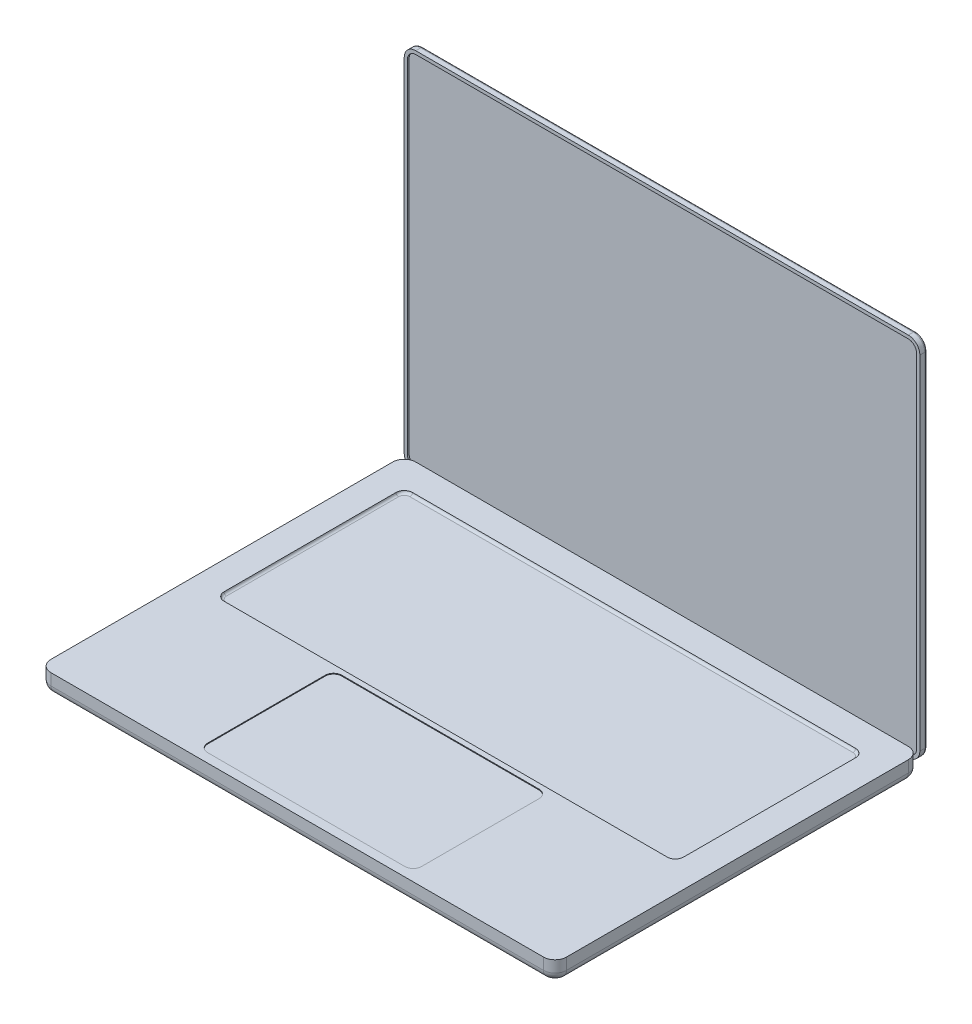
SolidWorks part; units mm, degrees
ref_plane "Front Plane" through (0, 0, 0) normal (0, 0, 1) x (1, 0, 0)
ref_plane "Top Plane" through (0, 0, 0) normal (0, 1, 0) x (1, 0, 0)
ref_plane "Right Plane" through (0, 0, 0) normal (1, 0, 0) x (0, 0, -1)
sketch "Sketch1" plane through (0, 0, 0) normal (0, 1, 0) x (1, 0, 0)
  line L1 (-149.337, -110.617) -> (149.337, -110.617)
  line L2 (-156.337, -103.617) -> (-156.337, 103.617)
  line L3 (-149.337, 110.617) -> (149.337, 110.617)
  line L4 (156.337, -103.617) -> (156.337, 103.617)
  line L5 (-156.337, -110.617) -> (156.337, 110.617) construction
  line L6 (-156.337, 110.617) -> (156.337, -110.617) construction
  arc A0 (149.337, 110.617) -> (156.337, 103.617) centre (149.337, 103.617) cw
  arc A1 (149.337, -110.617) -> (156.337, -103.617) centre (149.337, -103.617) ccw
  arc A2 (-149.337, -110.617) -> (-156.337, -103.617) centre (-149.337, -103.617) cw
  arc A3 (-156.337, 103.617) -> (-149.337, 110.617) centre (-149.337, 103.617) cw
  point P0 (0, 0)
  dimension "D3" = 7
  dimension "D1" = 221.234
  dimension "D2" = 312.674
extrude "Boss-Extrude1" add sketch "Sketch1" along normal blind 12
sketch "Sketch2" plane through (0, 0, -110.617) normal (0, 0, -1) x (-1, 0, 0)
  line L0 (0, 0) -> (0, 12) construction
  line L1 (-149.337, 6) -> (149.337, 6)
  line L2 (-156.337, 13) -> (-156.337, 221)
  line L3 (-149.337, 228) -> (149.337, 228)
  line L4 (156.337, 13) -> (156.337, 221)
  line L5 (-149.337, 12) -> (149.337, 12) construction
  line L6 (156.337, 12) -> (156.337, 0) construction
  arc A0 (-149.337, 6) -> (-156.337, 13) centre (-149.337, 13) cw
  arc A1 (149.337, 6) -> (156.337, 13) centre (149.337, 13) ccw
  arc A2 (149.337, 228) -> (156.337, 221) centre (149.337, 221) cw
  arc A3 (-156.337, 221) -> (-149.337, 228) centre (-149.337, 221) cw
  point P9 (0, 6)
  dimension "D2" = 7
  dimension "D1" = 222
extrude "Boss-Extrude2" add sketch "Sketch2" along normal blind 4.5
fillet "Fillet1" radius 5 8 edges at (0, 0, -110.617) (-154.2867, 0, -108.5667) (-156.337, 0, 0) (-154.2867, 0, 108.5667) (0, 0, 110.617) (154.2867, 0, 108.5667) (156.337, 0, 0) (154.2867, 0, -108.5667)
fillet "Fillet2" radius 1.5 8 edges at (156.337, 117, -115.117) (154.2867, 225.9497, -115.117) (0, 228, -115.117) (-154.2867, 225.9497, -115.117) (-156.337, 117, -115.117) (-154.2867, 8.0503, -115.117) (0, 6, -115.117) (154.2867, 8.0503, -115.117)
sketch "Sketch3" plane through (0, 0, -110.617) normal (0, 0, 1) x (1, 0, 0)
  line L6 (-151.337, 8.4174) -> (151.337, 8.4174)
  line L12 (-151.337, 14) -> (151.337, 14)
  line L13 (151.337, 14) -> (151.337, 8.4174)
  line L14 (154.337, 13) -> (154.337, 221)
  line L15 (149.337, 226) -> (-149.337, 226)
  line L16 (-154.337, 221) -> (-154.337, 13)
  line L17 (-151.337, 8.4174) -> (-151.337, 14)
  line L18 (-151.337, 14) -> (151.337, 14) construction
  line L19 (151.337, 14) -> (151.337, 8.4174) construction
  line L20 (154.337, 13) -> (154.337, 221)
  line L21 (149.337, 226) -> (-149.337, 226)
  line L22 (-154.337, 221) -> (-154.337, 13)
  line L23 (-151.337, 8.4174) -> (-151.337, 14) construction
  arc A8 (151.337, 8.4174) -> (154.337, 13) centre (149.337, 13) ccw
  arc A9 (154.337, 221) -> (149.337, 226) centre (149.337, 221) ccw
  arc A10 (-149.337, 226) -> (-154.337, 221) centre (-149.337, 221) ccw
  arc A11 (-154.337, 13) -> (-151.337, 8.4174) centre (-149.337, 13) ccw
  arc A12 (151.337, 8.4174) -> (154.337, 13) centre (149.337, 13) ccw
  arc A13 (154.337, 221) -> (149.337, 226) centre (149.337, 221) ccw
  arc A14 (-149.337, 226) -> (-154.337, 221) centre (-149.337, 221) ccw
  arc A15 (-154.337, 13) -> (-151.337, 8.4174) centre (-149.337, 13) ccw
  dimension "D1" = 2
extrude "Cut-Extrude1" cut sketch "Sketch3" against normal blind 1
sketch "Sketch4" plane through (0, 12, 0) normal (0, 1, 0) x (1, 0, 0)
  line L0 (-156.337, 103.617) -> (-156.337, -103.617) construction
  line L1 (-134.337, 93.617) -> (134.337, 93.617)
  line L2 (-139.337, 88.617) -> (-139.337, -15.617)
  line L3 (-134.337, -20.617) -> (134.337, -20.617)
  line L4 (139.337, 88.617) -> (139.337, -15.617)
  line L5 (-59.837, -23.767) -> (59.837, -23.767)
  line L6 (-64.837, -28.767) -> (-64.837, -100.117)
  line L7 (-59.837, -105.117) -> (59.837, -105.117)
  line L8 (64.837, -28.767) -> (64.837, -100.117)
  line L9 (156.337, -103.617) -> (156.337, 103.617) construction
  line L10 (149.337, 110.617) -> (-149.337, 110.617) construction
  line L11 (-149.337, -110.617) -> (149.337, -110.617) construction
  arc A0 (-139.337, -15.617) -> (-134.337, -20.617) centre (-134.337, -15.617) ccw
  arc A1 (-134.337, 93.617) -> (-139.337, 88.617) centre (-134.337, 88.617) ccw
  arc A2 (134.337, 93.617) -> (139.337, 88.617) centre (134.337, 88.617) cw
  arc A3 (134.337, -20.617) -> (139.337, -15.617) centre (134.337, -15.617) ccw
  arc A4 (59.837, -23.767) -> (64.837, -28.767) centre (59.837, -28.767) cw
  arc A5 (59.837, -105.117) -> (64.837, -100.117) centre (59.837, -100.117) ccw
  arc A6 (-64.837, -100.117) -> (-59.837, -105.117) centre (-59.837, -100.117) ccw
  arc A7 (-59.837, -23.767) -> (-64.837, -28.767) centre (-59.837, -28.767) ccw
  dimension "D9" = 5
  dimension "D1" = 17
  dimension "D2" = 17
  dimension "D3" = 17
  dimension "D4" = 90
  dimension "D5" = 3.15
  dimension "D6" = 5.5
  dimension "D7" = 91.5
  dimension "D8" = 91.5
extrude "Cut-Extrude2" cut sketch "Sketch4" against normal blind 1.5 contours L3 A3 L4 A2 L1 A1 L2 A0 region at (0, 12, -36.5)
extrude "Cut-Extrude3" cut sketch "Sketch4<3>" against normal blind 0.5 contours L5 A7 L6 A6 L7 A5 L8 A4 region at (0, 12, 64.442)
sketch "Sketch4<3>" plane through (0, 12, 0) normal (0, 1, 0) x (1, 0, 0) same geometry as "Sketch4"
fillet "Fillet3" radius 1.5 8 edges at (-137.8725, 10.5, -92.1525) (-139.337, 10.5, -36.5) (-137.8725, 10.5, 19.1525) (0, 10.5, 20.617) (137.8725, 10.5, 19.1525) (139.337, 10.5, -36.5) (137.8725, 10.5, -92.1525) (0, 10.5, -93.617)
